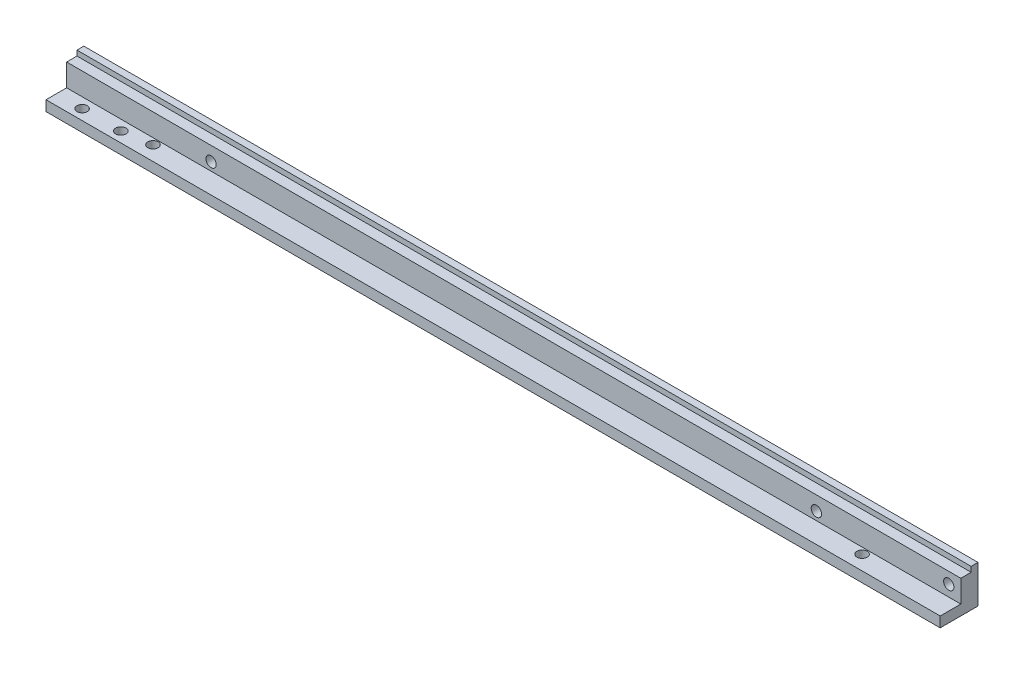
SolidWorks part; units mm, degrees
ref_plane "Спереди" through (0, 0, 0) normal (0, 0, 1) x (1, 0, 0)
ref_plane "Сверху" through (0, 0, 0) normal (0, 1, 0) x (1, 0, 0)
ref_plane "Справа" through (0, 0, 0) normal (1, 0, 0) x (0, 0, -1)
sketch "Эскиз1" plane through (0, 0, 0) normal (1, 0, 0) x (0, 0, -1)
  line L0 (0, 0) -> (-11, 0)
  line L1 (-11, 0) -> (-11, 3)
  line L2 (-11, 3) -> (-5, 3)
  line L3 (-5, 3) -> (-5, 9.5)
  line L4 (-5, 9.5) -> (-2, 9.5)
  line L5 (-2, 9.5) -> (-2, 11)
  line L6 (-2, 11) -> (0, 11)
  line L7 (0, 11) -> (0, 0)
  dimension "D1" = 5
  dimension "D2" = 11
  dimension "D3" = 3
  dimension "D4" = 6
  dimension "D5" = 6.5
  dimension "D6" = 11
  dimension "D7" = 1.5
  dimension "D8" = 2
extrude "Бобышка-Вытянуть1" add sketch "Эскиз1" along normal blind 260
sketch "Эскиз2" plane through (0, 0, 5) normal (0, 0, 1) x (1, 0, 0)
  line L1 (260, 9.5) -> (0, 9.5) construction
  line L2 (260, 9.5) -> (260, 3) construction
  circle A0 centre (256.5, 6.25) radius 1.5
  dimension "D1" = 3
  dimension "D2" = 3.5
  dimension "D3" = 3.25
extrude "Вырез-Вытянуть1" cut sketch "Эскиз2" against normal through all
sketch "Эскиз3" plane through (0, 3, 0) normal (0, 1, 0) x (1, 0, 0)
  line L1 (0, -5) -> (0, -11) construction
  line L2 (260, -11) -> (0, -11) construction
  circle A0 centre (7.5, -8) radius 1.5
  circle A1 centre (18.75, -8) radius 1.5
  dimension "D1" = 3
  dimension "D2" = 3
  dimension "D3" = 7.5
  dimension "D4" = 18.75
  dimension "D5" = 3
  dimension "D6" = 3
extrude "Вырез-Вытянуть2" cut sketch "Эскиз3" against normal through all
sketch "Эскиз4" plane through (0, 0, 5) normal (0, 0, 1) x (1, 0, 0)
  line L0 (0, 9.5) -> (0, 3) construction
  line L2 (260, 0) -> (0, 0) construction
  line L3 (130, 11) -> (130, -1.6462) construction
  line L4 (260, 11) -> (0, 11) construction
  circle A0 centre (42, 5.4) radius 1.5
  circle A1 centre (218, 5.4) radius 1.5
  dimension "D1" = 3
  dimension "D2" = 42
  dimension "D3" = 5.4
extrude "Вырез-Вытянуть3" cut sketch "Эскиз4" against normal through all
sketch "Эскиз5" plane through (0, 3, 0) normal (0, 1, 0) x (1, 0, 0)
  line L0 (0, -5) -> (0, -11) construction
  line L3 (260, -11) -> (0, -11) construction
  line L4 (130, -11) -> (130, 0) construction
  circle A0 centre (26.91, -6.8) radius 1.5
  circle A1 centre (233.09, -6.8) radius 1.5
  dimension "D1" = 3
  dimension "D2" = 26.91
  dimension "D3" = 4.2
extrude "Вырез-Вытянуть4" cut sketch "Эскиз5" against normal through all
